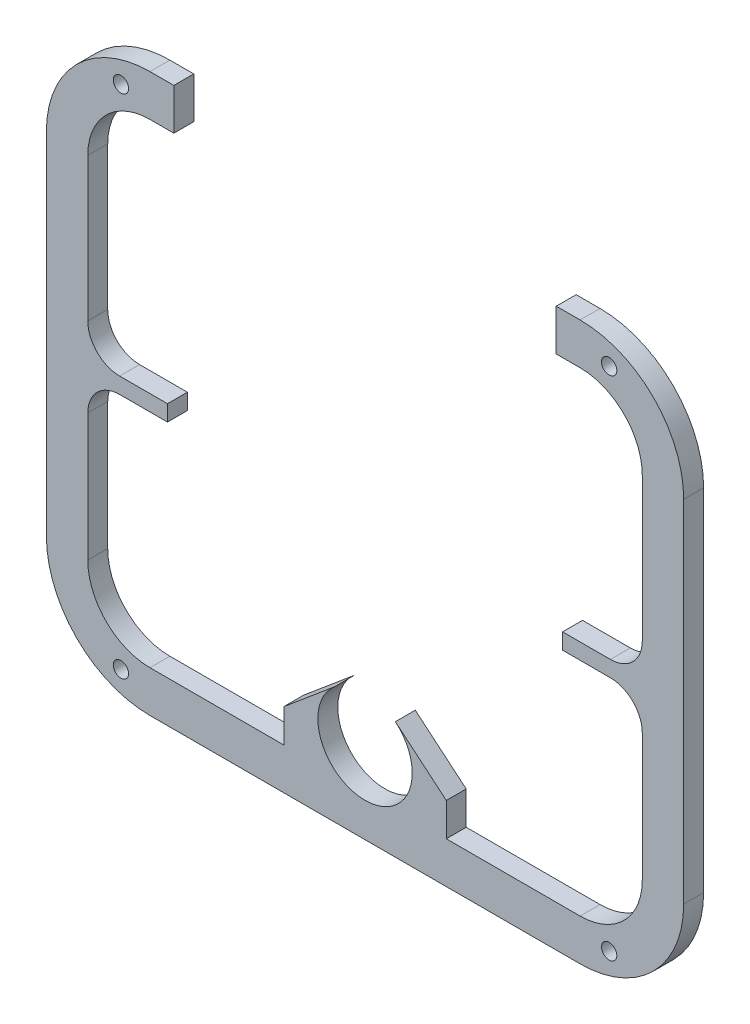
SolidWorks part; units mm, degrees
material "Delrin 2700 NC010, Low Viscosity Acetal Copolymer (SS)"
ref_plane "Front Plane" through (0, 0, 0) normal (0, 0, 1) x (1, 0, 0)
ref_plane "Top Plane" through (0, 0, 0) normal (0, 1, 0) x (1, 0, 0)
ref_plane "Right Plane" through (0, 0, 0) normal (1, 0, 0) x (0, 0, -1)
sketch "Sketch1" plane through (0, 0, 0) normal (0, 0, 1) x (1, 0, 0)
  line L0 (-17.145, -18.923) -> (-9.6321, -18.923)
  line L1 (17.145, 22.225) -> (-17.145, 22.225)
  line L2 (25.4, 13.97) -> (25.4, -13.97)
  line L3 (17.145, -22.225) -> (-17.145, -22.225)
  line L4 (-25.4, 13.97) -> (-25.4, -13.97)
  line L5 (25.4, 22.225) -> (-25.4, -22.225) construction
  line L6 (25.4, -22.225) -> (-25.4, 22.225) construction
  line L7 (9.6321, -18.923) -> (17.145, -18.923)
  line L8 (15.748, 0) -> (15.748, -1.27)
  line L9 (-22.098, 0) -> (-15.748, 0)
  line L10 (-22.098, 13.97) -> (-22.098, -13.97)
  line L11 (-1000, 0) -> (49000, 0) construction
  line L12 (-22.098, 0) -> (-22.098, -1.27)
  line L13 (22.098, 13.97) -> (22.098, -13.97)
  line L14 (17.145, 18.923) -> (-17.145, 18.923)
  line L15 (-22.098, -1.27) -> (-15.748, -1.27)
  line L16 (-15.748, 0) -> (-15.748, -1.27)
  line L17 (22.098, 0) -> (15.748, 0)
  line L18 (0, 18.923) -> (0, -18.415) construction
  line L19 (22.098, -1.27) -> (15.748, -1.27)
  line L21 (2.4164, -12.8683) -> (9.6321, -18.923)
  line L22 (-2.4164, -12.8683) -> (-9.6321, -18.923)
  line L36 (17.145, -18.923) -> (-17.145, -18.923) construction
  arc A0 (-2.4164, -12.8683) -> (2.4164, -12.8683) centre (0, -15.748) ccw
  arc A1 (-17.145, 22.225) -> (-25.4, 13.97) centre (-17.145, 13.97) ccw
  arc A2 (17.145, 22.225) -> (25.4, 13.97) centre (17.145, 13.97) cw
  arc A3 (25.4, -13.97) -> (17.145, -22.225) centre (17.145, -13.97) cw
  arc A4 (-17.145, -22.225) -> (-25.4, -13.97) centre (-17.145, -13.97) cw
  arc A7 (17.145, 18.923) -> (22.098, 13.97) centre (17.145, 13.97) cw
  arc A8 (-17.145, 18.923) -> (-22.098, 13.97) centre (-17.145, 13.97) ccw
  circle A9 centre (-19.4575, 20.193) radius 0.6096
  circle A10 centre (19.4575, 20.193) radius 0.6096
  circle A11 centre (-19.4575, -20.193) radius 0.6096
  circle A12 centre (19.4575, -20.193) radius 0.6096
  arc A13 (-17.145, -18.923) -> (-22.098, -13.97) centre (-17.145, -13.97) cw construction
  arc A14 (22.098, -13.97) -> (17.145, -18.923) centre (17.145, -13.97) cw construction
  arc A15 (-22.098, -13.97) -> (-17.145, -18.923) centre (-17.145, -13.97) ccw
  arc A16 (17.145, -18.923) -> (22.098, -13.97) centre (17.145, -13.97) ccw
  point P0 (0, 0)
  dimension "D4" = 7.5184
  dimension "D6" = 8.255
  dimension "D7" = 8.255
  dimension "D8" = 8.255
  dimension "D9" = 8.255
  dimension "D5" = 1.2192
  dimension "D1" = 50.8
  dimension "D2" = 44.45
  dimension "D10" = 3.302
  dimension "D3" = 3.175
  dimension "D11" = 2.032
  dimension "D12" = 19.4575
  dimension "D13" = 15.748
  dimension "D14" = 1.27
  dimension "D15" = 6.35
extrude "Boss-Extrude1" add sketch "Sketch1" along normal blind 1.5875 contours A4 L3 A3 L2 A2 L1 A1 L4 A16 L7 L21 A0 L22 L0 A15 L10 A8 L14 A7 L13 A12 A10 A9 A11 | L16 L9 L10 L15 | L19 L13 L17 L8 region at (-18.923, -0.635, 0) region at (18.923, -0.635, 0) region at (22.5049, 19.3299, 0)
sketch "Sketch2" plane through (0, 0, 1.5875) normal (0, 0, 1) x (1, 0, 0)
  line L1 (-9.6321, -18.923) -> (-6.477, -18.923)
  line L2 (-9.6321, -18.923) -> (-9.6321, -16.2756)
  line L3 (-9.6321, -16.2756) -> (-6.477, -16.2756)
  line L4 (-6.477, -18.923) -> (-6.477, -16.2756)
  line L5 (0, -1000) -> (0, 49000) construction
  line L6 (9.6321, -18.923) -> (9.6321, -16.2756)
  line L7 (9.6321, -16.2756) -> (6.477, -16.2756)
  line L8 (6.477, -18.923) -> (6.477, -16.2756)
  line L9 (9.6321, -18.923) -> (6.477, -18.923)
  line L11 (-15.24, 18.923) -> (15.24, 18.923)
  line L12 (-15.24, 18.923) -> (-15.24, 22.225)
  line L13 (-15.24, 22.225) -> (15.24, 22.225)
  line L14 (15.24, 18.923) -> (15.24, 22.225)
  line L16 (17.145, 18.923) -> (-17.145, 18.923) construction
  line L17 (-2.4164, -12.8683) -> (-9.6321, -18.923) construction
  line L18 (17.145, 22.225) -> (-17.145, 22.225) construction
  point P25 (0, 22.225)
  dimension "D1" = 6.477
  dimension "D2" = 30.48
extrude "Cut-Extrude1" cut sketch "Sketch2" against normal up to next
fillet "Fillet1" radius 2.54 4 edges at (22.098, -1.27, 0.7937) (22.098, 0, 0.7937) (-22.098, 0, 0.7937) (-22.098, -1.27, 0.7937)
